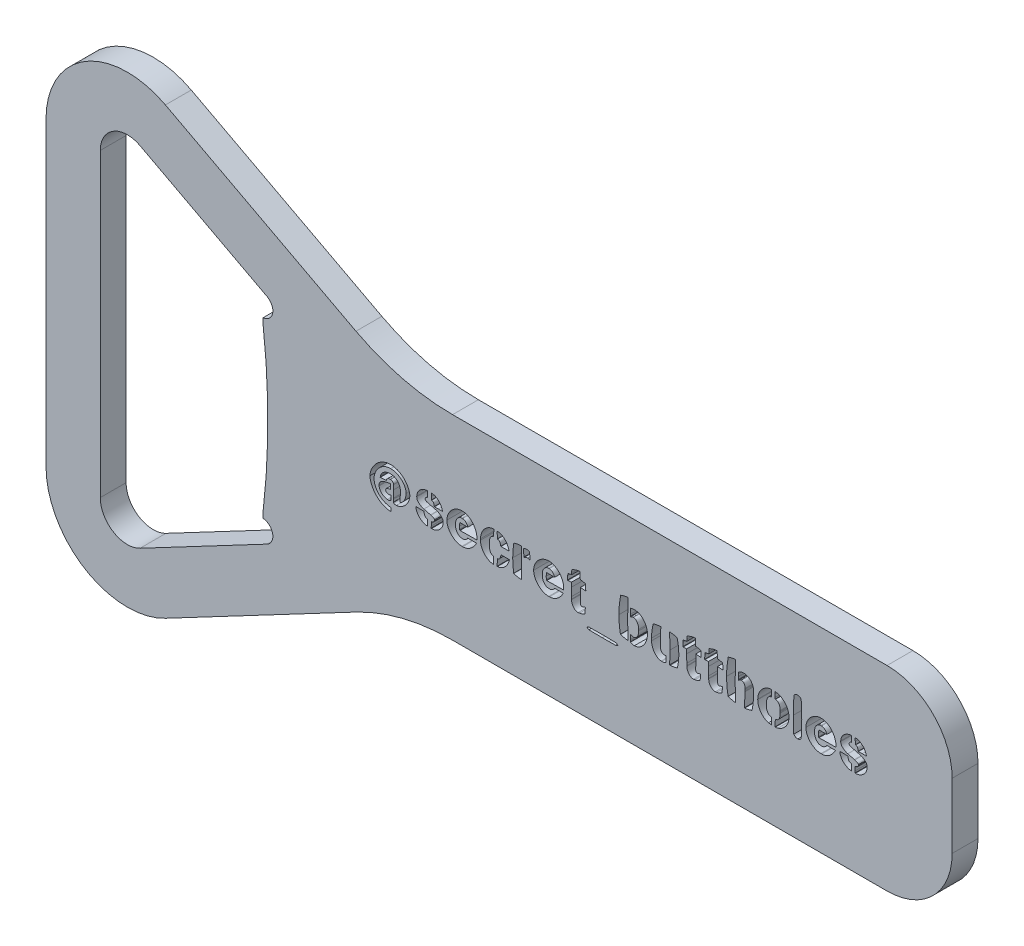
SolidWorks part; units mm, degrees
ref_plane "Front Plane" through (0, 0, 0) normal (0, 0, 1) x (1, 0, 0)
ref_plane "Top Plane" through (0, 0, 0) normal (0, 1, 0) x (1, 0, 0)
ref_plane "Right Plane" through (0, 0, 0) normal (1, 0, 0) x (0, 0, -1)
sketch "Model" plane through (0, 0, 0) normal (0, 0, 1) x (1, 0, 0)
  line L0 (93.451, 245.0307) -> (75.8892, 254.3082)
  line L1 (64.8859, 247.6767) -> (64.8859, 219.9729)
  line L2 (75.8892, 213.3414) -> (93.451, 222.6188)
  line L3 (102.3493, 224.8248) -> (142.3859, 224.8248)
  line L4 (73.5537, 217.7624) -> (85.2574, 223.9452)
  line L5 (69.8859, 247.6767) -> (69.8859, 219.9729)
  line L6 (85.2574, 243.7044) -> (73.5537, 249.8872)
  line L7 (84.8859, 225.8248) -> (84.8859, 226.3248)
  line L8 (84.8859, 241.3248) -> (84.8859, 241.8248)
  line L9 (142.3859, 242.8248) -> (102.3493, 242.8248)
  line L10 (148.3859, 230.8248) -> (148.3859, 236.8248)
  arc A0 (93.451, 245.0307) -> (102.3493, 242.8248) centre (102.3493, 261.8748) ccw
  arc A1 (75.8892, 254.3082) -> (64.8859, 247.6767) centre (72.3859, 247.6767) ccw
  arc A2 (64.8859, 219.9729) -> (75.8892, 213.3414) centre (72.3859, 219.9729) ccw
  arc A3 (102.3493, 224.8248) -> (93.451, 222.6188) centre (102.3493, 205.7748) ccw
  arc A4 (69.8859, 219.9729) -> (73.5537, 217.7624) centre (72.3859, 219.9729) ccw
  arc A5 (73.5537, 249.8872) -> (69.8859, 247.6767) centre (72.3859, 247.6767) ccw
  arc A6 (85.2574, 223.9452) -> (85.7424, 225.1352) centre (84.7903, 224.8294) ccw
  arc A7 (85.7424, 242.5144) -> (85.2574, 243.7044) centre (84.7903, 242.8202) ccw
  arc A9 (85.7424, 225.1352) -> (84.8859, 225.8248) centre (84.7903, 224.8294) ccw
  arc A10 (84.8859, 226.3248) -> (84.8859, 241.3248) centre (21.8304, 233.8248) ccw
  arc A11 (84.8859, 241.8248) -> (85.7424, 242.5144) centre (84.7903, 242.8202) ccw
  arc A12 (148.3859, 236.8248) -> (142.3859, 242.8248) centre (142.3859, 236.8248) ccw
  arc A13 (142.3859, 224.8248) -> (148.3859, 230.8248) centre (142.3859, 230.8248) ccw
extrude "Boss-Extrude1" add sketch "Model" along normal blind 2.3813
sketch "Sketch2" plane through (0, 0, 2.3813) normal (0, 0, 1) x (1, 0, 0)
  line L0 (148.3859, 232.7854) -> (85.3219, 232.7854) construction
  line L1 (148.3859, 230.8248) -> (148.3859, 236.8248) construction
  arc A0 (84.8859, 226.3248) -> (84.8859, 241.3248) centre (21.8304, 233.8248) ccw construction
  text T0 "@secret_buttholes     " font "Stencilia-Bold" height 3.5
  point P8 (0, 0)
  point P9 (148.3859, 234.5359)
extrude "Cut-Extrude1" cut sketch "Sketch2" against normal through all
